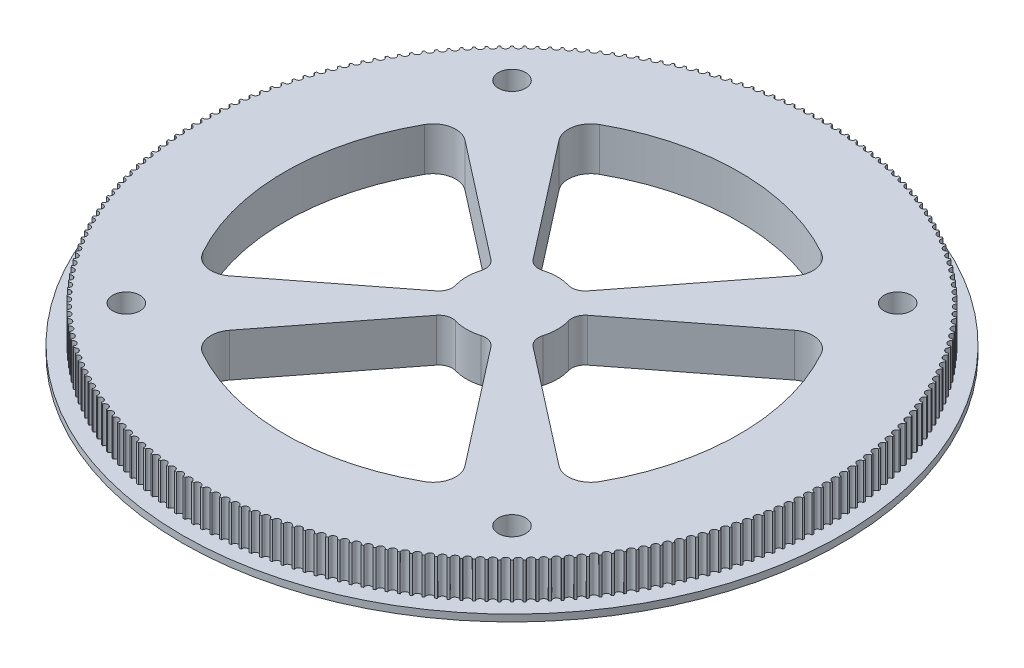
SolidWorks part; units mm, degrees
material "ABS"
ref_plane "Front Plane" through (0, 0, 0) normal (0, 0, 1) x (1, 0, 0)
ref_plane "Top Plane" through (0, 0, 0) normal (0, 1, 0) x (1, 0, 0)
ref_plane "Right Plane" through (0, 0, 0) normal (1, 0, 0) x (0, 0, -1)
sketch "Sketch1" plane through (0, 0, 0) normal (0, 1, 0) x (1, 0, 0)
  arc A0 (-0.76, 69.2508) -> (-1.2179, 69.2443) centre (0, 0) ccw
  arc A1 (-0.76, 69.2508) -> (0.76, 69.2508) centre (0, 69.255) ccw
  arc A2 (1.2179, 69.2443) -> (2.7372, 69.2009) centre (1.9776, 69.2268) ccw
  arc A3 (3.1947, 69.1813) -> (4.7122, 69.0945) centre (3.9537, 69.1421) ccw
  arc A4 (5.1689, 69.0618) -> (6.6833, 68.9318) centre (5.9265, 69.001) ccw
  arc A5 (7.139, 68.8861) -> (8.649, 68.7128) centre (7.8945, 68.8036) ccw
  arc A6 (9.1032, 68.6541) -> (10.6077, 68.4378) centre (9.856, 68.5501) ccw
  arc A7 (11.0599, 68.3662) -> (12.5577, 68.107) centre (11.8095, 68.2407) ccw
  arc A8 (13.0077, 68.0225) -> (14.4974, 67.7206) centre (13.7534, 67.8756) ccw
  arc A9 (14.9449, 67.6233) -> (16.4253, 67.279) centre (15.686, 67.4552) ccw
  arc A10 (16.8698, 67.1689) -> (18.3399, 66.7825) centre (17.6059, 66.9798) ccw
  arc A11 (18.781, 66.6598) -> (20.2394, 66.2316) centre (19.5114, 66.4497) ccw
  arc A12 (20.6769, 66.0963) -> (22.1225, 65.6266) centre (21.401, 65.8654) ccw
  arc A13 (22.5559, 65.4789) -> (23.9875, 64.9681) centre (23.2731, 65.2274) ccw
  arc A14 (24.4165, 64.8081) -> (25.8329, 64.2566) centre (25.1262, 64.5362) ccw
  arc A15 (26.2572, 64.0844) -> (27.6573, 63.4927) centre (26.9589, 63.7924) ccw
  arc A16 (28.0765, 63.3085) -> (29.4591, 62.6771) centre (28.7696, 62.9966) ccw
  arc A17 (29.8729, 62.4809) -> (31.2369, 61.8103) centre (30.5568, 62.1493) ccw
  arc A18 (31.6449, 61.6024) -> (32.9893, 60.8931) centre (32.319, 61.2514) ccw
  arc A19 (33.3912, 60.6736) -> (34.7147, 59.9262) centre (34.055, 60.3035) ccw
  arc A20 (35.1101, 59.6953) -> (36.4118, 58.9104) centre (35.7631, 59.3065) ccw
  arc A21 (36.8005, 58.6684) -> (38.0792, 57.8466) centre (37.4421, 58.261) ccw
  arc A22 (38.4608, 57.5936) -> (39.7155, 56.7356) centre (39.0905, 57.1681) ccw
  arc A23 (40.0898, 56.4718) -> (41.3195, 55.5784) centre (40.7071, 56.0285) ccw
  arc A24 (41.686, 55.304) -> (42.8897, 54.3758) centre (42.2904, 54.8432) ccw
  arc A25 (43.2483, 54.091) -> (44.425, 53.1289) centre (43.8393, 53.6132) ccw
  arc A26 (44.7753, 52.834) -> (45.924, 51.8386) centre (45.3524, 52.3394) ccw
  arc A27 (46.2658, 51.5338) -> (47.3856, 50.5061) centre (46.8285, 51.023) ccw
  arc A28 (47.7185, 50.1916) -> (48.8085, 49.1323) centre (48.2664, 49.665) ccw
  arc A29 (49.1323, 48.8085) -> (50.1916, 47.7185) centre (49.665, 48.2664) ccw
  arc A30 (50.5061, 47.3856) -> (51.5338, 46.2658) centre (51.023, 46.8285) ccw
  arc A31 (51.8386, 45.924) -> (52.834, 44.7753) centre (52.3394, 45.3524) ccw
  arc A32 (53.1289, 44.425) -> (54.091, 43.2483) centre (53.6132, 43.8393) ccw
  arc A33 (54.3758, 42.8897) -> (55.304, 41.686) centre (54.8432, 42.2904) ccw
  arc A34 (55.5784, 41.3195) -> (56.4718, 40.0898) centre (56.0285, 40.7071) ccw
  arc A35 (56.7356, 39.7155) -> (57.5936, 38.4608) centre (57.1681, 39.0905) ccw
  arc A36 (57.8466, 38.0792) -> (58.6684, 36.8005) centre (58.261, 37.4421) ccw
  arc A37 (58.9104, 36.4118) -> (59.6953, 35.1101) centre (59.3065, 35.7631) ccw
  arc A38 (59.9262, 34.7147) -> (60.6736, 33.3912) centre (60.3035, 34.055) ccw
  arc A39 (60.8931, 32.9893) -> (61.6024, 31.6449) centre (61.2514, 32.319) ccw
  arc A40 (61.8103, 31.2369) -> (62.4809, 29.8729) centre (62.1493, 30.5568) ccw
  arc A41 (62.6771, 29.4591) -> (63.3085, 28.0765) centre (62.9966, 28.7696) ccw
  arc A42 (63.4927, 27.6573) -> (64.0844, 26.2572) centre (63.7924, 26.9589) ccw
  arc A43 (64.2566, 25.8329) -> (64.8081, 24.4165) centre (64.5362, 25.1262) ccw
  arc A44 (64.9681, 23.9875) -> (65.4789, 22.5559) centre (65.2274, 23.2731) ccw
  arc A45 (65.6266, 22.1225) -> (66.0963, 20.6769) centre (65.8654, 21.401) ccw
  arc A46 (66.2316, 20.2394) -> (66.6598, 18.781) centre (66.4497, 19.5114) ccw
  arc A47 (66.7825, 18.3399) -> (67.1689, 16.8698) centre (66.9798, 17.6059) ccw
  arc A48 (67.279, 16.4253) -> (67.6233, 14.9449) centre (67.4552, 15.686) ccw
  arc A49 (67.7206, 14.4974) -> (68.0225, 13.0077) centre (67.8756, 13.7534) ccw
  arc A50 (68.107, 12.5577) -> (68.3662, 11.0599) centre (68.2407, 11.8095) ccw
  arc A51 (68.4378, 10.6077) -> (68.6541, 9.1032) centre (68.5501, 9.856) ccw
  arc A52 (68.7128, 8.649) -> (68.8861, 7.139) centre (68.8036, 7.8945) ccw
  arc A53 (68.9318, 6.6833) -> (69.0618, 5.1689) centre (69.001, 5.9265) ccw
  arc A54 (69.0945, 4.7122) -> (69.1813, 3.1947) centre (69.1421, 3.9537) ccw
  arc A55 (69.2009, 2.7372) -> (69.2443, 1.2179) centre (69.2268, 1.9776) ccw
  arc A56 (69.2508, 0.76) -> (69.2508, -0.76) centre (69.255, 0) ccw
  arc A57 (69.2443, -1.2179) -> (69.2009, -2.7372) centre (69.2268, -1.9776) ccw
  arc A58 (69.1813, -3.1947) -> (69.0945, -4.7122) centre (69.1421, -3.9537) ccw
  arc A59 (69.0618, -5.1689) -> (68.9318, -6.6833) centre (69.001, -5.9265) ccw
  arc A60 (68.8861, -7.139) -> (68.7128, -8.649) centre (68.8036, -7.8945) ccw
  arc A61 (68.6541, -9.1032) -> (68.4378, -10.6077) centre (68.5501, -9.856) ccw
  arc A62 (68.3662, -11.0599) -> (68.107, -12.5577) centre (68.2407, -11.8095) ccw
  arc A63 (68.0225, -13.0077) -> (67.7206, -14.4974) centre (67.8756, -13.7534) ccw
  arc A64 (67.6233, -14.9449) -> (67.279, -16.4253) centre (67.4552, -15.686) ccw
  arc A65 (67.1689, -16.8698) -> (66.7825, -18.3399) centre (66.9798, -17.6059) ccw
  arc A66 (66.6598, -18.781) -> (66.2316, -20.2394) centre (66.4497, -19.5114) ccw
  arc A67 (66.0963, -20.6769) -> (65.6266, -22.1225) centre (65.8654, -21.401) ccw
  arc A68 (65.4789, -22.5559) -> (64.9681, -23.9875) centre (65.2274, -23.2731) ccw
  arc A69 (64.8081, -24.4165) -> (64.2566, -25.8329) centre (64.5362, -25.1262) ccw
  arc A70 (64.0844, -26.2572) -> (63.4927, -27.6573) centre (63.7924, -26.9589) ccw
  arc A71 (63.3085, -28.0765) -> (62.6771, -29.4591) centre (62.9966, -28.7696) ccw
  arc A72 (62.4809, -29.8729) -> (61.8103, -31.2369) centre (62.1493, -30.5568) ccw
  arc A73 (61.6024, -31.6449) -> (60.8931, -32.9893) centre (61.2514, -32.319) ccw
  arc A74 (60.6736, -33.3912) -> (59.9262, -34.7147) centre (60.3035, -34.055) ccw
  arc A75 (59.6953, -35.1101) -> (58.9104, -36.4118) centre (59.3065, -35.7631) ccw
  arc A76 (58.6684, -36.8005) -> (57.8466, -38.0792) centre (58.261, -37.4421) ccw
  arc A77 (57.5936, -38.4608) -> (56.7356, -39.7155) centre (57.1681, -39.0905) ccw
  arc A78 (56.4718, -40.0898) -> (55.5784, -41.3195) centre (56.0285, -40.7071) ccw
  arc A79 (55.304, -41.686) -> (54.3758, -42.8897) centre (54.8432, -42.2904) ccw
  arc A80 (54.091, -43.2483) -> (53.1289, -44.425) centre (53.6132, -43.8393) ccw
  arc A81 (52.834, -44.7753) -> (51.8386, -45.924) centre (52.3394, -45.3524) ccw
  arc A82 (51.5338, -46.2658) -> (50.5061, -47.3856) centre (51.023, -46.8285) ccw
  arc A83 (50.1916, -47.7185) -> (49.1323, -48.8085) centre (49.665, -48.2664) ccw
  arc A84 (48.8085, -49.1323) -> (47.7185, -50.1916) centre (48.2664, -49.665) ccw
  arc A85 (47.3856, -50.5061) -> (46.2658, -51.5338) centre (46.8285, -51.023) ccw
  arc A86 (45.924, -51.8386) -> (44.7753, -52.834) centre (45.3524, -52.3394) ccw
  arc A87 (44.425, -53.1289) -> (43.2483, -54.091) centre (43.8393, -53.6132) ccw
  arc A88 (42.8897, -54.3758) -> (41.686, -55.304) centre (42.2904, -54.8432) ccw
  arc A89 (41.3195, -55.5784) -> (40.0898, -56.4718) centre (40.7071, -56.0285) ccw
  arc A90 (39.7155, -56.7356) -> (38.4608, -57.5936) centre (39.0905, -57.1681) ccw
  arc A91 (38.0792, -57.8466) -> (36.8005, -58.6684) centre (37.4421, -58.261) ccw
  arc A92 (36.4118, -58.9104) -> (35.1101, -59.6953) centre (35.7631, -59.3065) ccw
  arc A93 (34.7147, -59.9262) -> (33.3912, -60.6736) centre (34.055, -60.3035) ccw
  arc A94 (32.9893, -60.8931) -> (31.6449, -61.6024) centre (32.319, -61.2514) ccw
  arc A95 (31.2369, -61.8103) -> (29.8729, -62.4809) centre (30.5568, -62.1493) ccw
  arc A96 (29.4591, -62.6771) -> (28.0765, -63.3085) centre (28.7696, -62.9966) ccw
  arc A97 (27.6573, -63.4927) -> (26.2572, -64.0844) centre (26.9589, -63.7924) ccw
  arc A98 (25.8329, -64.2566) -> (24.4165, -64.8081) centre (25.1262, -64.5362) ccw
  arc A99 (23.9875, -64.9681) -> (22.5559, -65.4789) centre (23.2731, -65.2274) ccw
  arc A100 (22.1225, -65.6266) -> (20.6769, -66.0963) centre (21.401, -65.8654) ccw
  arc A101 (20.2394, -66.2316) -> (18.781, -66.6598) centre (19.5114, -66.4497) ccw
  arc A102 (18.3399, -66.7825) -> (16.8698, -67.1689) centre (17.6059, -66.9798) ccw
  arc A103 (16.4253, -67.279) -> (14.9449, -67.6233) centre (15.686, -67.4552) ccw
  arc A104 (14.4974, -67.7206) -> (13.0077, -68.0225) centre (13.7534, -67.8756) ccw
  arc A105 (12.5577, -68.107) -> (11.0599, -68.3662) centre (11.8095, -68.2407) ccw
  arc A106 (10.6077, -68.4378) -> (9.1032, -68.6541) centre (9.856, -68.5501) ccw
  arc A107 (8.649, -68.7128) -> (7.139, -68.8861) centre (7.8945, -68.8036) ccw
  arc A108 (6.6833, -68.9318) -> (5.1689, -69.0618) centre (5.9265, -69.001) ccw
  arc A109 (4.7122, -69.0945) -> (3.1947, -69.1813) centre (3.9537, -69.1421) ccw
  arc A110 (2.7372, -69.2009) -> (1.2179, -69.2443) centre (1.9776, -69.2268) ccw
  arc A111 (0.76, -69.2508) -> (-0.76, -69.2508) centre (0, -69.255) ccw
  arc A112 (-1.2179, -69.2443) -> (-2.7372, -69.2009) centre (-1.9776, -69.2268) ccw
  arc A113 (-3.1947, -69.1813) -> (-4.7122, -69.0945) centre (-3.9537, -69.1421) ccw
  arc A114 (-5.1689, -69.0618) -> (-6.6833, -68.9318) centre (-5.9265, -69.001) ccw
  arc A115 (-7.139, -68.8861) -> (-8.649, -68.7128) centre (-7.8945, -68.8036) ccw
  arc A116 (-9.1032, -68.6541) -> (-10.6077, -68.4378) centre (-9.856, -68.5501) ccw
  arc A117 (-11.0599, -68.3662) -> (-12.5577, -68.107) centre (-11.8095, -68.2407) ccw
  arc A118 (-13.0077, -68.0225) -> (-14.4974, -67.7206) centre (-13.7534, -67.8756) ccw
  arc A119 (-14.9449, -67.6233) -> (-16.4253, -67.279) centre (-15.686, -67.4552) ccw
  arc A120 (-16.8698, -67.1689) -> (-18.3399, -66.7825) centre (-17.6059, -66.9798) ccw
  arc A121 (-18.781, -66.6598) -> (-20.2394, -66.2316) centre (-19.5114, -66.4497) ccw
  arc A122 (-20.6769, -66.0963) -> (-22.1225, -65.6266) centre (-21.401, -65.8654) ccw
  arc A123 (-22.5559, -65.4789) -> (-23.9875, -64.9681) centre (-23.2731, -65.2274) ccw
  arc A124 (-24.4165, -64.8081) -> (-25.8329, -64.2566) centre (-25.1262, -64.5362) ccw
  arc A125 (-26.2572, -64.0844) -> (-27.6573, -63.4927) centre (-26.9589, -63.7924) ccw
  arc A126 (-28.0765, -63.3085) -> (-29.4591, -62.6771) centre (-28.7696, -62.9966) ccw
  arc A127 (-29.8729, -62.4809) -> (-31.2369, -61.8103) centre (-30.5568, -62.1493) ccw
  arc A128 (-31.6449, -61.6024) -> (-32.9893, -60.8931) centre (-32.319, -61.2514) ccw
  arc A129 (-33.3912, -60.6736) -> (-34.7147, -59.9262) centre (-34.055, -60.3035) ccw
  arc A130 (-35.1101, -59.6953) -> (-36.4118, -58.9104) centre (-35.7631, -59.3065) ccw
  arc A131 (-36.8005, -58.6684) -> (-38.0792, -57.8466) centre (-37.4421, -58.261) ccw
  arc A132 (-38.4608, -57.5936) -> (-39.7155, -56.7356) centre (-39.0905, -57.1681) ccw
  arc A133 (-40.0898, -56.4718) -> (-41.3195, -55.5784) centre (-40.7071, -56.0285) ccw
  arc A134 (-41.686, -55.304) -> (-42.8897, -54.3758) centre (-42.2904, -54.8432) ccw
  arc A135 (-43.2483, -54.091) -> (-44.425, -53.1289) centre (-43.8393, -53.6132) ccw
  arc A136 (-44.7753, -52.834) -> (-45.924, -51.8386) centre (-45.3524, -52.3394) ccw
  arc A137 (-46.2658, -51.5338) -> (-47.3856, -50.5061) centre (-46.8285, -51.023) ccw
  arc A138 (-47.7185, -50.1916) -> (-48.8085, -49.1323) centre (-48.2664, -49.665) ccw
  arc A139 (-49.1323, -48.8085) -> (-50.1916, -47.7185) centre (-49.665, -48.2664) ccw
  arc A140 (-50.5061, -47.3856) -> (-51.5338, -46.2658) centre (-51.023, -46.8285) ccw
  arc A141 (-51.8386, -45.924) -> (-52.834, -44.7753) centre (-52.3394, -45.3524) ccw
  arc A142 (-53.1289, -44.425) -> (-54.091, -43.2483) centre (-53.6132, -43.8393) ccw
  arc A143 (-54.3758, -42.8897) -> (-55.304, -41.686) centre (-54.8432, -42.2904) ccw
  arc A144 (-55.5784, -41.3195) -> (-56.4718, -40.0898) centre (-56.0285, -40.7071) ccw
  arc A145 (-56.7356, -39.7155) -> (-57.5936, -38.4608) centre (-57.1681, -39.0905) ccw
  arc A146 (-57.8466, -38.0792) -> (-58.6684, -36.8005) centre (-58.261, -37.4421) ccw
  arc A147 (-58.9104, -36.4118) -> (-59.6953, -35.1101) centre (-59.3065, -35.7631) ccw
  arc A148 (-59.9262, -34.7147) -> (-60.6736, -33.3912) centre (-60.3035, -34.055) ccw
  arc A149 (-60.8931, -32.9893) -> (-61.6024, -31.6449) centre (-61.2514, -32.319) ccw
  arc A150 (-61.8103, -31.2369) -> (-62.4809, -29.8729) centre (-62.1493, -30.5568) ccw
  arc A151 (-62.6771, -29.4591) -> (-63.3085, -28.0765) centre (-62.9966, -28.7696) ccw
  arc A152 (-63.4927, -27.6573) -> (-64.0844, -26.2572) centre (-63.7924, -26.9589) ccw
  arc A153 (-64.2566, -25.8329) -> (-64.8081, -24.4165) centre (-64.5362, -25.1262) ccw
  arc A154 (-64.9681, -23.9875) -> (-65.4789, -22.5559) centre (-65.2274, -23.2731) ccw
  arc A155 (-65.6266, -22.1225) -> (-66.0963, -20.6769) centre (-65.8654, -21.401) ccw
  arc A156 (-66.2316, -20.2394) -> (-66.6598, -18.781) centre (-66.4497, -19.5114) ccw
  arc A157 (-66.7825, -18.3399) -> (-67.1689, -16.8698) centre (-66.9798, -17.6059) ccw
  arc A158 (-67.279, -16.4253) -> (-67.6233, -14.9449) centre (-67.4552, -15.686) ccw
  arc A159 (-67.7206, -14.4974) -> (-68.0225, -13.0077) centre (-67.8756, -13.7534) ccw
  arc A160 (-68.107, -12.5577) -> (-68.3662, -11.0599) centre (-68.2407, -11.8095) ccw
  arc A161 (-68.4378, -10.6077) -> (-68.6541, -9.1032) centre (-68.5501, -9.856) ccw
  arc A162 (-68.7128, -8.649) -> (-68.8861, -7.139) centre (-68.8036, -7.8945) ccw
  arc A163 (-68.9318, -6.6833) -> (-69.0618, -5.1689) centre (-69.001, -5.9265) ccw
  arc A164 (-69.0945, -4.7122) -> (-69.1813, -3.1947) centre (-69.1421, -3.9537) ccw
  arc A165 (-69.2009, -2.7372) -> (-69.2443, -1.2179) centre (-69.2268, -1.9776) ccw
  arc A166 (-69.2508, -0.76) -> (-69.2508, 0.76) centre (-69.255, 0) ccw
  arc A167 (-69.2443, 1.2179) -> (-69.2009, 2.7372) centre (-69.2268, 1.9776) ccw
  arc A168 (-69.1813, 3.1947) -> (-69.0945, 4.7122) centre (-69.1421, 3.9537) ccw
  arc A169 (-69.0618, 5.1689) -> (-68.9318, 6.6833) centre (-69.001, 5.9265) ccw
  arc A170 (-68.8861, 7.139) -> (-68.7128, 8.649) centre (-68.8036, 7.8945) ccw
  arc A171 (-68.6541, 9.1032) -> (-68.4378, 10.6077) centre (-68.5501, 9.856) ccw
  arc A172 (-68.3662, 11.0599) -> (-68.107, 12.5577) centre (-68.2407, 11.8095) ccw
  arc A173 (-68.0225, 13.0077) -> (-67.7206, 14.4974) centre (-67.8756, 13.7534) ccw
  arc A174 (-67.6233, 14.9449) -> (-67.279, 16.4253) centre (-67.4552, 15.686) ccw
  arc A175 (-67.1689, 16.8698) -> (-66.7825, 18.3399) centre (-66.9798, 17.6059) ccw
  arc A176 (-66.6598, 18.781) -> (-66.2316, 20.2394) centre (-66.4497, 19.5114) ccw
  arc A177 (-66.0963, 20.6769) -> (-65.6266, 22.1225) centre (-65.8654, 21.401) ccw
  arc A178 (-65.4789, 22.5559) -> (-64.9681, 23.9875) centre (-65.2274, 23.2731) ccw
  arc A179 (-64.8081, 24.4165) -> (-64.2566, 25.8329) centre (-64.5362, 25.1262) ccw
  arc A180 (-64.0844, 26.2572) -> (-63.4927, 27.6573) centre (-63.7924, 26.9589) ccw
  arc A181 (-63.3085, 28.0765) -> (-62.6771, 29.4591) centre (-62.9966, 28.7696) ccw
  arc A182 (-62.4809, 29.8729) -> (-61.8103, 31.2369) centre (-62.1493, 30.5568) ccw
  arc A183 (-61.6024, 31.6449) -> (-60.8931, 32.9893) centre (-61.2514, 32.319) ccw
  arc A184 (-60.6736, 33.3912) -> (-59.9262, 34.7147) centre (-60.3035, 34.055) ccw
  arc A185 (-59.6953, 35.1101) -> (-58.9104, 36.4118) centre (-59.3065, 35.7631) ccw
  arc A186 (-58.6684, 36.8005) -> (-57.8466, 38.0792) centre (-58.261, 37.4421) ccw
  arc A187 (-57.5936, 38.4608) -> (-56.7356, 39.7155) centre (-57.1681, 39.0905) ccw
  arc A188 (-56.4718, 40.0898) -> (-55.5784, 41.3195) centre (-56.0285, 40.7071) ccw
  arc A189 (-55.304, 41.686) -> (-54.3758, 42.8897) centre (-54.8432, 42.2904) ccw
  arc A190 (-54.091, 43.2483) -> (-53.1289, 44.425) centre (-53.6132, 43.8393) ccw
  arc A191 (-52.834, 44.7753) -> (-51.8386, 45.924) centre (-52.3394, 45.3524) ccw
  arc A192 (-51.5338, 46.2658) -> (-50.5061, 47.3856) centre (-51.023, 46.8285) ccw
  arc A193 (-50.1916, 47.7185) -> (-49.1323, 48.8085) centre (-49.665, 48.2664) ccw
  arc A194 (-48.8085, 49.1323) -> (-47.7185, 50.1916) centre (-48.2664, 49.665) ccw
  arc A195 (-47.3856, 50.5061) -> (-46.2658, 51.5338) centre (-46.8285, 51.023) ccw
  arc A196 (-45.924, 51.8386) -> (-44.7753, 52.834) centre (-45.3524, 52.3394) ccw
  arc A197 (-44.425, 53.1289) -> (-43.2483, 54.091) centre (-43.8393, 53.6132) ccw
  arc A198 (-42.8897, 54.3758) -> (-41.686, 55.304) centre (-42.2904, 54.8432) ccw
  arc A199 (-41.3195, 55.5784) -> (-40.0898, 56.4718) centre (-40.7071, 56.0285) ccw
  arc A200 (-39.7155, 56.7356) -> (-38.4608, 57.5936) centre (-39.0905, 57.1681) ccw
  arc A201 (-38.0792, 57.8466) -> (-36.8005, 58.6684) centre (-37.4421, 58.261) ccw
  arc A202 (-36.4118, 58.9104) -> (-35.1101, 59.6953) centre (-35.7631, 59.3065) ccw
  arc A203 (-34.7147, 59.9262) -> (-33.3912, 60.6736) centre (-34.055, 60.3035) ccw
  arc A204 (-32.9893, 60.8931) -> (-31.6449, 61.6024) centre (-32.319, 61.2514) ccw
  arc A205 (-31.2369, 61.8103) -> (-29.8729, 62.4809) centre (-30.5568, 62.1493) ccw
  arc A206 (-29.4591, 62.6771) -> (-28.0765, 63.3085) centre (-28.7696, 62.9966) ccw
  arc A207 (-27.6573, 63.4927) -> (-26.2572, 64.0844) centre (-26.9589, 63.7924) ccw
  arc A208 (-25.8329, 64.2566) -> (-24.4165, 64.8081) centre (-25.1262, 64.5362) ccw
  arc A209 (-23.9875, 64.9681) -> (-22.5559, 65.4789) centre (-23.2731, 65.2274) ccw
  arc A210 (-22.1225, 65.6266) -> (-20.6769, 66.0963) centre (-21.401, 65.8654) ccw
  arc A211 (-20.2394, 66.2316) -> (-18.781, 66.6598) centre (-19.5114, 66.4497) ccw
  arc A212 (-18.3399, 66.7825) -> (-16.8698, 67.1689) centre (-17.6059, 66.9798) ccw
  arc A213 (-16.4253, 67.279) -> (-14.9449, 67.6233) centre (-15.686, 67.4552) ccw
  arc A214 (-14.4974, 67.7206) -> (-13.0077, 68.0225) centre (-13.7534, 67.8756) ccw
  arc A215 (-12.5577, 68.107) -> (-11.0599, 68.3662) centre (-11.8095, 68.2407) ccw
  arc A216 (-10.6077, 68.4378) -> (-9.1032, 68.6541) centre (-9.856, 68.5501) ccw
  arc A217 (-8.649, 68.7128) -> (-7.139, 68.8861) centre (-7.8945, 68.8036) ccw
  arc A218 (-6.6833, 68.9318) -> (-5.1689, 69.0618) centre (-5.9265, 69.001) ccw
  arc A219 (-4.7122, 69.0945) -> (-3.1947, 69.1813) centre (-3.9537, 69.1421) ccw
  arc A220 (-2.7372, 69.2009) -> (-1.2179, 69.2443) centre (-1.9776, 69.2268) ccw
  arc A221 (1.2179, 69.2443) -> (0.76, 69.2508) centre (0, 0) ccw
  arc A222 (3.1947, 69.1813) -> (2.7372, 69.2009) centre (0, 0) ccw
  arc A223 (5.1689, 69.0618) -> (4.7122, 69.0945) centre (0, 0) ccw
  arc A224 (7.139, 68.8861) -> (6.6833, 68.9318) centre (0, 0) ccw
  arc A225 (9.1032, 68.6541) -> (8.649, 68.7128) centre (0, 0) ccw
  arc A226 (11.0599, 68.3662) -> (10.6077, 68.4378) centre (0, 0) ccw
  arc A227 (13.0077, 68.0225) -> (12.5577, 68.107) centre (0, 0) ccw
  arc A228 (14.9449, 67.6233) -> (14.4974, 67.7206) centre (0, 0) ccw
  arc A229 (16.8698, 67.1689) -> (16.4253, 67.279) centre (0, 0) ccw
  arc A230 (18.781, 66.6598) -> (18.3399, 66.7825) centre (0, 0) ccw
  arc A231 (20.6769, 66.0963) -> (20.2394, 66.2316) centre (0, 0) ccw
  arc A232 (22.5559, 65.4789) -> (22.1225, 65.6266) centre (0, 0) ccw
  arc A233 (24.4165, 64.8081) -> (23.9875, 64.9681) centre (0, 0) ccw
  arc A234 (26.2572, 64.0844) -> (25.8329, 64.2566) centre (0, 0) ccw
  arc A235 (28.0765, 63.3085) -> (27.6573, 63.4927) centre (0, 0) ccw
  arc A236 (29.8729, 62.4809) -> (29.4591, 62.6771) centre (0, 0) ccw
  arc A237 (31.6449, 61.6024) -> (31.2369, 61.8103) centre (0, 0) ccw
  arc A238 (33.3912, 60.6736) -> (32.9893, 60.8931) centre (0, 0) ccw
  arc A239 (35.1101, 59.6953) -> (34.7147, 59.9262) centre (0, 0) ccw
  arc A240 (36.8005, 58.6684) -> (36.4118, 58.9104) centre (0, 0) ccw
  arc A241 (38.4608, 57.5936) -> (38.0792, 57.8466) centre (0, 0) ccw
  arc A242 (40.0898, 56.4718) -> (39.7155, 56.7356) centre (0, 0) ccw
  arc A243 (41.686, 55.304) -> (41.3195, 55.5784) centre (0, 0) ccw
  arc A244 (43.2483, 54.091) -> (42.8897, 54.3758) centre (0, 0) ccw
  arc A245 (44.7753, 52.834) -> (44.425, 53.1289) centre (0, 0) ccw
  arc A246 (46.2658, 51.5338) -> (45.924, 51.8386) centre (0, 0) ccw
  arc A247 (47.7185, 50.1916) -> (47.3856, 50.5061) centre (0, 0) ccw
  arc A248 (49.1323, 48.8085) -> (48.8085, 49.1323) centre (0, 0) ccw
  arc A249 (50.5061, 47.3856) -> (50.1916, 47.7185) centre (0, 0) ccw
  arc A250 (51.8386, 45.924) -> (51.5338, 46.2658) centre (0, 0) ccw
  arc A251 (53.1289, 44.425) -> (52.834, 44.7753) centre (0, 0) ccw
  arc A252 (54.3758, 42.8897) -> (54.091, 43.2483) centre (0, 0) ccw
  arc A253 (55.5784, 41.3195) -> (55.304, 41.686) centre (0, 0) ccw
  arc A254 (56.7356, 39.7155) -> (56.4718, 40.0898) centre (0, 0) ccw
  arc A255 (57.8466, 38.0792) -> (57.5936, 38.4608) centre (0, 0) ccw
  arc A256 (58.9104, 36.4118) -> (58.6684, 36.8005) centre (0, 0) ccw
  arc A257 (59.9262, 34.7147) -> (59.6953, 35.1101) centre (0, 0) ccw
  arc A258 (60.8931, 32.9893) -> (60.6736, 33.3912) centre (0, 0) ccw
  arc A259 (61.8103, 31.2369) -> (61.6024, 31.6449) centre (0, 0) ccw
  arc A260 (62.6771, 29.4591) -> (62.4809, 29.8729) centre (0, 0) ccw
  arc A261 (63.4927, 27.6573) -> (63.3085, 28.0765) centre (0, 0) ccw
  arc A262 (64.2566, 25.8329) -> (64.0844, 26.2572) centre (0, 0) ccw
  arc A263 (64.9681, 23.9875) -> (64.8081, 24.4165) centre (0, 0) ccw
  arc A264 (65.6266, 22.1225) -> (65.4789, 22.5559) centre (0, 0) ccw
  arc A265 (66.2316, 20.2394) -> (66.0963, 20.6769) centre (0, 0) ccw
  arc A266 (66.7825, 18.3399) -> (66.6598, 18.781) centre (0, 0) ccw
  arc A267 (67.279, 16.4253) -> (67.1689, 16.8698) centre (0, 0) ccw
  arc A268 (67.7206, 14.4974) -> (67.6233, 14.9449) centre (0, 0) ccw
  arc A269 (68.107, 12.5577) -> (68.0225, 13.0077) centre (0, 0) ccw
  arc A270 (68.4378, 10.6077) -> (68.3662, 11.0599) centre (0, 0) ccw
  arc A271 (68.7128, 8.649) -> (68.6541, 9.1032) centre (0, 0) ccw
  arc A272 (68.9318, 6.6833) -> (68.8861, 7.139) centre (0, 0) ccw
  arc A273 (69.0945, 4.7122) -> (69.0618, 5.1689) centre (0, 0) ccw
  arc A274 (69.2009, 2.7372) -> (69.1813, 3.1947) centre (0, 0) ccw
  arc A275 (69.2508, 0.76) -> (69.2443, 1.2179) centre (0, 0) ccw
  arc A276 (69.2443, -1.2179) -> (69.2508, -0.76) centre (0, 0) ccw
  arc A277 (69.1813, -3.1947) -> (69.2009, -2.7372) centre (0, 0) ccw
  arc A278 (69.0618, -5.1689) -> (69.0945, -4.7122) centre (0, 0) ccw
  arc A279 (68.8861, -7.139) -> (68.9318, -6.6833) centre (0, 0) ccw
  arc A280 (68.6541, -9.1032) -> (68.7128, -8.649) centre (0, 0) ccw
  arc A281 (68.3662, -11.0599) -> (68.4378, -10.6077) centre (0, 0) ccw
  arc A282 (68.0225, -13.0077) -> (68.107, -12.5577) centre (0, 0) ccw
  arc A283 (67.6233, -14.9449) -> (67.7206, -14.4974) centre (0, 0) ccw
  arc A284 (67.1689, -16.8698) -> (67.279, -16.4253) centre (0, 0) ccw
  arc A285 (66.6598, -18.781) -> (66.7825, -18.3399) centre (0, 0) ccw
  arc A286 (66.0963, -20.6769) -> (66.2316, -20.2394) centre (0, 0) ccw
  arc A287 (65.4789, -22.5559) -> (65.6266, -22.1225) centre (0, 0) ccw
  arc A288 (64.8081, -24.4165) -> (64.9681, -23.9875) centre (0, 0) ccw
  arc A289 (64.0844, -26.2572) -> (64.2566, -25.8329) centre (0, 0) ccw
  arc A290 (63.3085, -28.0765) -> (63.4927, -27.6573) centre (0, 0) ccw
  arc A291 (62.4809, -29.8729) -> (62.6771, -29.4591) centre (0, 0) ccw
  arc A292 (61.6024, -31.6449) -> (61.8103, -31.2369) centre (0, 0) ccw
  arc A293 (60.6736, -33.3912) -> (60.8931, -32.9893) centre (0, 0) ccw
  arc A294 (59.6953, -35.1101) -> (59.9262, -34.7147) centre (0, 0) ccw
  arc A295 (58.6684, -36.8005) -> (58.9104, -36.4118) centre (0, 0) ccw
  arc A296 (57.5936, -38.4608) -> (57.8466, -38.0792) centre (0, 0) ccw
  arc A297 (56.4718, -40.0898) -> (56.7356, -39.7155) centre (0, 0) ccw
  arc A298 (55.304, -41.686) -> (55.5784, -41.3195) centre (0, 0) ccw
  arc A299 (54.091, -43.2483) -> (54.3758, -42.8897) centre (0, 0) ccw
  arc A300 (52.834, -44.7753) -> (53.1289, -44.425) centre (0, 0) ccw
  arc A301 (51.5338, -46.2658) -> (51.8386, -45.924) centre (0, 0) ccw
  arc A302 (50.1916, -47.7185) -> (50.5061, -47.3856) centre (0, 0) ccw
  arc A303 (48.8085, -49.1323) -> (49.1323, -48.8085) centre (0, 0) ccw
  arc A304 (47.3856, -50.5061) -> (47.7185, -50.1916) centre (0, 0) ccw
  arc A305 (45.924, -51.8386) -> (46.2658, -51.5338) centre (0, 0) ccw
  arc A306 (44.425, -53.1289) -> (44.7753, -52.834) centre (0, 0) ccw
  arc A307 (42.8897, -54.3758) -> (43.2483, -54.091) centre (0, 0) ccw
  arc A308 (41.3195, -55.5784) -> (41.686, -55.304) centre (0, 0) ccw
  arc A309 (39.7155, -56.7356) -> (40.0898, -56.4718) centre (0, 0) ccw
  arc A310 (38.0792, -57.8466) -> (38.4608, -57.5936) centre (0, 0) ccw
  arc A311 (36.4118, -58.9104) -> (36.8005, -58.6684) centre (0, 0) ccw
  arc A312 (34.7147, -59.9262) -> (35.1101, -59.6953) centre (0, 0) ccw
  arc A313 (32.9893, -60.8931) -> (33.3912, -60.6736) centre (0, 0) ccw
  arc A314 (31.2369, -61.8103) -> (31.6449, -61.6024) centre (0, 0) ccw
  arc A315 (29.4591, -62.6771) -> (29.8729, -62.4809) centre (0, 0) ccw
  arc A316 (27.6573, -63.4927) -> (28.0765, -63.3085) centre (0, 0) ccw
  arc A317 (23.9875, -64.9681) -> (24.4165, -64.8081) centre (0, 0) ccw
  arc A318 (25.8329, -64.2566) -> (26.2572, -64.0844) centre (0, 0) ccw
  arc A319 (22.1225, -65.6266) -> (22.5559, -65.4789) centre (0, 0) ccw
  arc A320 (20.2394, -66.2316) -> (20.6769, -66.0963) centre (0, 0) ccw
  arc A321 (18.3399, -66.7825) -> (18.781, -66.6598) centre (0, 0) ccw
  arc A322 (16.4253, -67.279) -> (16.8698, -67.1689) centre (0, 0) ccw
  arc A323 (14.4974, -67.7206) -> (14.9449, -67.6233) centre (0, 0) ccw
  arc A324 (12.5577, -68.107) -> (13.0077, -68.0225) centre (0, 0) ccw
  arc A325 (10.6077, -68.4378) -> (11.0599, -68.3662) centre (0, 0) ccw
  arc A326 (8.649, -68.7128) -> (9.1032, -68.6541) centre (0, 0) ccw
  arc A327 (6.6833, -68.9318) -> (7.139, -68.8861) centre (0, 0) ccw
  arc A328 (4.7122, -69.0945) -> (5.1689, -69.0618) centre (0, 0) ccw
  arc A329 (2.7372, -69.2009) -> (3.1947, -69.1813) centre (0, 0) ccw
  arc A330 (0.76, -69.2508) -> (1.2179, -69.2443) centre (0, 0) ccw
  arc A331 (-1.2179, -69.2443) -> (-0.76, -69.2508) centre (0, 0) ccw
  arc A332 (-3.1947, -69.1813) -> (-2.7372, -69.2009) centre (0, 0) ccw
  arc A333 (-5.1689, -69.0618) -> (-4.7122, -69.0945) centre (0, 0) ccw
  arc A334 (-7.139, -68.8861) -> (-6.6833, -68.9318) centre (0, 0) ccw
  arc A335 (-9.1032, -68.6541) -> (-8.649, -68.7128) centre (0, 0) ccw
  arc A336 (-11.0599, -68.3662) -> (-10.6077, -68.4378) centre (0, 0) ccw
  arc A337 (-13.0077, -68.0225) -> (-12.5577, -68.107) centre (0, 0) ccw
  arc A338 (-14.9449, -67.6233) -> (-14.4974, -67.7206) centre (0, 0) ccw
  arc A339 (-16.8698, -67.1689) -> (-16.4253, -67.279) centre (0, 0) ccw
  arc A340 (-18.781, -66.6598) -> (-18.3399, -66.7825) centre (0, 0) ccw
  arc A341 (-20.6769, -66.0963) -> (-20.2394, -66.2316) centre (0, 0) ccw
  arc A342 (-22.5559, -65.4789) -> (-22.1225, -65.6266) centre (0, 0) ccw
  arc A343 (-24.4165, -64.8081) -> (-23.9875, -64.9681) centre (0, 0) ccw
  arc A344 (-26.2572, -64.0844) -> (-25.8329, -64.2566) centre (0, 0) ccw
  arc A345 (-28.0765, -63.3085) -> (-27.6573, -63.4927) centre (0, 0) ccw
  arc A346 (-29.8729, -62.4809) -> (-29.4591, -62.6771) centre (0, 0) ccw
  arc A347 (-31.6449, -61.6024) -> (-31.2369, -61.8103) centre (0, 0) ccw
  arc A348 (-33.3912, -60.6736) -> (-32.9893, -60.8931) centre (0, 0) ccw
  arc A349 (-35.1101, -59.6953) -> (-34.7147, -59.9262) centre (0, 0) ccw
  arc A350 (-36.8005, -58.6684) -> (-36.4118, -58.9104) centre (0, 0) ccw
  arc A351 (-38.4608, -57.5936) -> (-38.0792, -57.8466) centre (0, 0) ccw
  arc A352 (-40.0898, -56.4718) -> (-39.7155, -56.7356) centre (0, 0) ccw
  arc A353 (-41.686, -55.304) -> (-41.3195, -55.5784) centre (0, 0) ccw
  arc A354 (-43.2483, -54.091) -> (-42.8897, -54.3758) centre (0, 0) ccw
  arc A355 (-44.7753, -52.834) -> (-44.425, -53.1289) centre (0, 0) ccw
  arc A356 (-46.2658, -51.5338) -> (-45.924, -51.8386) centre (0, 0) ccw
  arc A357 (-47.7185, -50.1916) -> (-47.3856, -50.5061) centre (0, 0) ccw
  arc A358 (-49.1323, -48.8085) -> (-48.8085, -49.1323) centre (0, 0) ccw
  arc A359 (-50.5061, -47.3856) -> (-50.1916, -47.7185) centre (0, 0) ccw
  arc A360 (-51.8386, -45.924) -> (-51.5338, -46.2658) centre (0, 0) ccw
  arc A361 (-53.1289, -44.425) -> (-52.834, -44.7753) centre (0, 0) ccw
  arc A362 (-54.3758, -42.8897) -> (-54.091, -43.2483) centre (0, 0) ccw
  arc A363 (-55.5784, -41.3195) -> (-55.304, -41.686) centre (0, 0) ccw
  arc A364 (-56.7356, -39.7155) -> (-56.4718, -40.0898) centre (0, 0) ccw
  arc A365 (-57.8466, -38.0792) -> (-57.5936, -38.4608) centre (0, 0) ccw
  arc A366 (-58.9104, -36.4118) -> (-58.6684, -36.8005) centre (0, 0) ccw
  arc A367 (-59.9262, -34.7147) -> (-59.6953, -35.1101) centre (0, 0) ccw
  arc A368 (-60.8931, -32.9893) -> (-60.6736, -33.3912) centre (0, 0) ccw
  arc A369 (-61.8103, -31.2369) -> (-61.6024, -31.6449) centre (0, 0) ccw
  arc A370 (-62.6771, -29.4591) -> (-62.4809, -29.8729) centre (0, 0) ccw
  arc A371 (-63.4927, -27.6573) -> (-63.3085, -28.0765) centre (0, 0) ccw
  arc A372 (-64.2566, -25.8329) -> (-64.0844, -26.2572) centre (0, 0) ccw
  arc A373 (-64.9681, -23.9875) -> (-64.8081, -24.4165) centre (0, 0) ccw
  arc A374 (-65.6266, -22.1225) -> (-65.4789, -22.5559) centre (0, 0) ccw
  arc A375 (-66.2316, -20.2394) -> (-66.0963, -20.6769) centre (0, 0) ccw
  arc A376 (-66.7825, -18.3399) -> (-66.6598, -18.781) centre (0, 0) ccw
  arc A377 (-67.279, -16.4253) -> (-67.1689, -16.8698) centre (0, 0) ccw
  arc A378 (-67.7206, -14.4974) -> (-67.6233, -14.9449) centre (0, 0) ccw
  arc A379 (-68.107, -12.5577) -> (-68.0225, -13.0077) centre (0, 0) ccw
  arc A380 (-68.4378, -10.6077) -> (-68.3662, -11.0599) centre (0, 0) ccw
  arc A381 (-68.7128, -8.649) -> (-68.6541, -9.1032) centre (0, 0) ccw
  arc A382 (-68.9318, -6.6833) -> (-68.8861, -7.139) centre (0, 0) ccw
  arc A383 (-69.0945, -4.7122) -> (-69.0618, -5.1689) centre (0, 0) ccw
  arc A384 (-69.2009, -2.7372) -> (-69.1813, -3.1947) centre (0, 0) ccw
  arc A385 (-69.2508, -0.76) -> (-69.2443, -1.2179) centre (0, 0) ccw
  arc A386 (-69.2443, 1.2179) -> (-69.2508, 0.76) centre (0, 0) ccw
  arc A387 (-69.1813, 3.1947) -> (-69.2009, 2.7372) centre (0, 0) ccw
  arc A388 (-69.0618, 5.1689) -> (-69.0945, 4.7122) centre (0, 0) ccw
  arc A389 (-68.8861, 7.139) -> (-68.9318, 6.6833) centre (0, 0) ccw
  arc A390 (-68.6541, 9.1032) -> (-68.7128, 8.649) centre (0, 0) ccw
  arc A391 (-68.3662, 11.0599) -> (-68.4378, 10.6077) centre (0, 0) ccw
  arc A392 (-68.0225, 13.0077) -> (-68.107, 12.5577) centre (0, 0) ccw
  arc A393 (-67.6233, 14.9449) -> (-67.7206, 14.4974) centre (0, 0) ccw
  arc A394 (-67.1689, 16.8698) -> (-67.279, 16.4253) centre (0, 0) ccw
  arc A395 (-66.6598, 18.781) -> (-66.7825, 18.3399) centre (0, 0) ccw
  arc A396 (-66.0963, 20.6769) -> (-66.2316, 20.2394) centre (0, 0) ccw
  arc A397 (-65.4789, 22.5559) -> (-65.6266, 22.1225) centre (0, 0) ccw
  arc A398 (-64.8081, 24.4165) -> (-64.9681, 23.9875) centre (0, 0) ccw
  arc A399 (-64.0844, 26.2572) -> (-64.2566, 25.8329) centre (0, 0) ccw
  arc A400 (-63.3085, 28.0765) -> (-63.4927, 27.6573) centre (0, 0) ccw
  arc A401 (-62.4809, 29.8729) -> (-62.6771, 29.4591) centre (0, 0) ccw
  arc A402 (-61.6024, 31.6449) -> (-61.8103, 31.2369) centre (0, 0) ccw
  arc A403 (-60.6736, 33.3912) -> (-60.8931, 32.9893) centre (0, 0) ccw
  arc A404 (-59.6953, 35.1101) -> (-59.9262, 34.7147) centre (0, 0) ccw
  arc A405 (-58.6684, 36.8005) -> (-58.9104, 36.4118) centre (0, 0) ccw
  arc A406 (-57.5936, 38.4608) -> (-57.8466, 38.0792) centre (0, 0) ccw
  arc A407 (-56.4718, 40.0898) -> (-56.7356, 39.7155) centre (0, 0) ccw
  arc A408 (-55.304, 41.686) -> (-55.5784, 41.3195) centre (0, 0) ccw
  arc A409 (-54.091, 43.2483) -> (-54.3758, 42.8897) centre (0, 0) ccw
  arc A410 (-52.834, 44.7753) -> (-53.1289, 44.425) centre (0, 0) ccw
  arc A411 (-51.5338, 46.2658) -> (-51.8386, 45.924) centre (0, 0) ccw
  arc A412 (-50.1916, 47.7185) -> (-50.5061, 47.3856) centre (0, 0) ccw
  arc A413 (-48.8085, 49.1323) -> (-49.1323, 48.8085) centre (0, 0) ccw
  arc A414 (-47.3856, 50.5061) -> (-47.7185, 50.1916) centre (0, 0) ccw
  arc A415 (-45.924, 51.8386) -> (-46.2658, 51.5338) centre (0, 0) ccw
  arc A416 (-42.8897, 54.3758) -> (-43.2483, 54.091) centre (0, 0) ccw
  arc A417 (-44.425, 53.1289) -> (-44.7753, 52.834) centre (0, 0) ccw
  arc A418 (-41.3195, 55.5784) -> (-41.686, 55.304) centre (0, 0) ccw
  arc A419 (-39.7155, 56.7356) -> (-40.0898, 56.4718) centre (0, 0) ccw
  arc A420 (-38.0792, 57.8466) -> (-38.4608, 57.5936) centre (0, 0) ccw
  arc A421 (-36.4118, 58.9104) -> (-36.8005, 58.6684) centre (0, 0) ccw
  arc A422 (-34.7147, 59.9262) -> (-35.1101, 59.6953) centre (0, 0) ccw
  arc A423 (-32.9893, 60.8931) -> (-33.3912, 60.6736) centre (0, 0) ccw
  arc A424 (-31.2369, 61.8103) -> (-31.6449, 61.6024) centre (0, 0) ccw
  arc A425 (-29.4591, 62.6771) -> (-29.8729, 62.4809) centre (0, 0) ccw
  arc A426 (-27.6573, 63.4927) -> (-28.0765, 63.3085) centre (0, 0) ccw
  arc A427 (-25.8329, 64.2566) -> (-26.2572, 64.0844) centre (0, 0) ccw
  arc A428 (-23.9875, 64.9681) -> (-24.4165, 64.8081) centre (0, 0) ccw
  arc A429 (-22.1225, 65.6266) -> (-22.5559, 65.4789) centre (0, 0) ccw
  arc A430 (-20.2394, 66.2316) -> (-20.6769, 66.0963) centre (0, 0) ccw
  arc A431 (-18.3399, 66.7825) -> (-18.781, 66.6598) centre (0, 0) ccw
  arc A432 (-16.4253, 67.279) -> (-16.8698, 67.1689) centre (0, 0) ccw
  arc A433 (-14.4974, 67.7206) -> (-14.9449, 67.6233) centre (0, 0) ccw
  arc A434 (-12.5577, 68.107) -> (-13.0077, 68.0225) centre (0, 0) ccw
  arc A435 (-8.649, 68.7128) -> (-9.1032, 68.6541) centre (0, 0) ccw
  arc A436 (-10.6077, 68.4378) -> (-11.0599, 68.3662) centre (0, 0) ccw
  arc A437 (-6.6833, 68.9318) -> (-7.139, 68.8861) centre (0, 0) ccw
  arc A438 (-4.7122, 69.0945) -> (-5.1689, 69.0618) centre (0, 0) ccw
  arc A439 (-2.7372, 69.2009) -> (-3.1947, 69.1813) centre (0, 0) ccw
  point P665 (0, 0)
  dimension "D1" = 138.51
  dimension "D2" = 1.52
  dimension "D3" = 220
extrude "Boss-Extrude1" add sketch "Sketch1" along normal blind 8
sketch "Sketch3" plane through (0, 0, 0) normal (0, -1, 0) x (1, 0, 0)
  circle A0 centre (0, 0) radius 72.5
extrude "Boss-Extrude3" add sketch "Sketch3" along normal blind 1.5
sketch "Sketch6" plane through (0, 8, 0) normal (0, 1, 0) x (1, 0, 0)
  line L5 (-42.425, 42.425) -> (42.425, -42.425) construction
  line L6 (-42.425, -42.425) -> (42.425, 42.425) construction
  circle A0 centre (42.425, 42.425) radius 3
  circle A1 centre (42.425, -42.425) radius 3
  circle A2 centre (-42.425, -42.425) radius 3
  circle A3 centre (-42.425, 42.425) radius 3
  point P0 (0, 0)
  dimension "D3" = 6
  dimension "D1" = 84.85
  dimension "D2" = 84.85
extrude "Cut-Extrude3" cut sketch "Sketch6" against normal through all
sketch "Sketch7" plane through (0, 8, 0) normal (0, 1, 0) x (1, 0, 0)
  line L0 (0, 0) -> (42.425, 42.425) construction
  line L1 (29.243, 40.5567) -> (4.624, 8.8667)
  line L2 (40.5567, 29.243) -> (8.8667, 4.624)
  line L3 (4.624, 8.8667) -> (6.7454, 6.7454) construction
  line L4 (6.7454, 6.7454) -> (8.8667, 4.624) construction
  line L5 (29.243, 40.5567) -> (34.8999, 34.8999) construction
  line L6 (40.5567, 29.243) -> (34.8999, 34.8999) construction
  line L7 (29.243, -40.5567) -> (4.624, -8.8667)
  line L8 (40.5567, -29.243) -> (8.8667, -4.624)
  line L9 (-40.5567, -29.243) -> (-8.8667, -4.624)
  line L10 (-29.243, -40.5567) -> (-4.624, -8.8667)
  line L11 (-29.243, 40.5567) -> (-4.624, 8.8667)
  line L12 (-40.5567, 29.243) -> (-8.8667, 4.624)
  arc A0 (-40.5567, 29.243) -> (-40.5567, -29.243) centre (0, 0) ccw
  arc A1 (-8.8667, 4.624) -> (-8.8667, -4.624) centre (0, 0) ccw
  arc A2 (-29.243, -40.5567) -> (29.243, -40.5567) centre (0, 0) ccw
  arc A3 (40.5567, -29.243) -> (40.5567, 29.243) centre (0, 0) ccw
  arc A4 (29.243, 40.5567) -> (-29.243, 40.5567) centre (0, 0) ccw
  arc A5 (-4.624, -8.8667) -> (4.624, -8.8667) centre (0, 0) ccw
  arc A6 (8.8667, -4.624) -> (8.8667, 4.624) centre (0, 0) ccw
  arc A7 (4.624, 8.8667) -> (-4.624, 8.8667) centre (0, 0) ccw
  point P27 (-0.4923, 0.4115)
  point P28 (0, 0)
  dimension "D1" = 100
  dimension "D2" = 20
  dimension "D3" = 3
  dimension "D4" = 8
  dimension "D5" = 8
  dimension "D6" = 4
extrude "Cut-Extrude4" cut sketch "Sketch7" against normal through all
fillet "Fillet1" radius 3 8 edges at (-8.8667, 3.25, 4.624) (-8.8667, 3.25, -4.624) (-4.624, 3.25, -8.8667) (4.624, 3.25, -8.8667) (8.8667, 3.25, -4.624) (8.8667, 3.25, 4.624) (4.624, 3.25, 8.8667) (-4.624, 3.25, 8.8667)
fillet "Fillet2" radius 5 8 edges at (-40.5567, 3.25, -29.243) (-40.5567, 3.25, 29.243) (-29.243, 3.25, 40.5567) (29.243, 3.25, 40.5567) (40.5567, 3.25, 29.243) (40.5567, 3.25, -29.243) (29.243, 3.25, -40.5567) (-29.243, 3.25, -40.5567)
